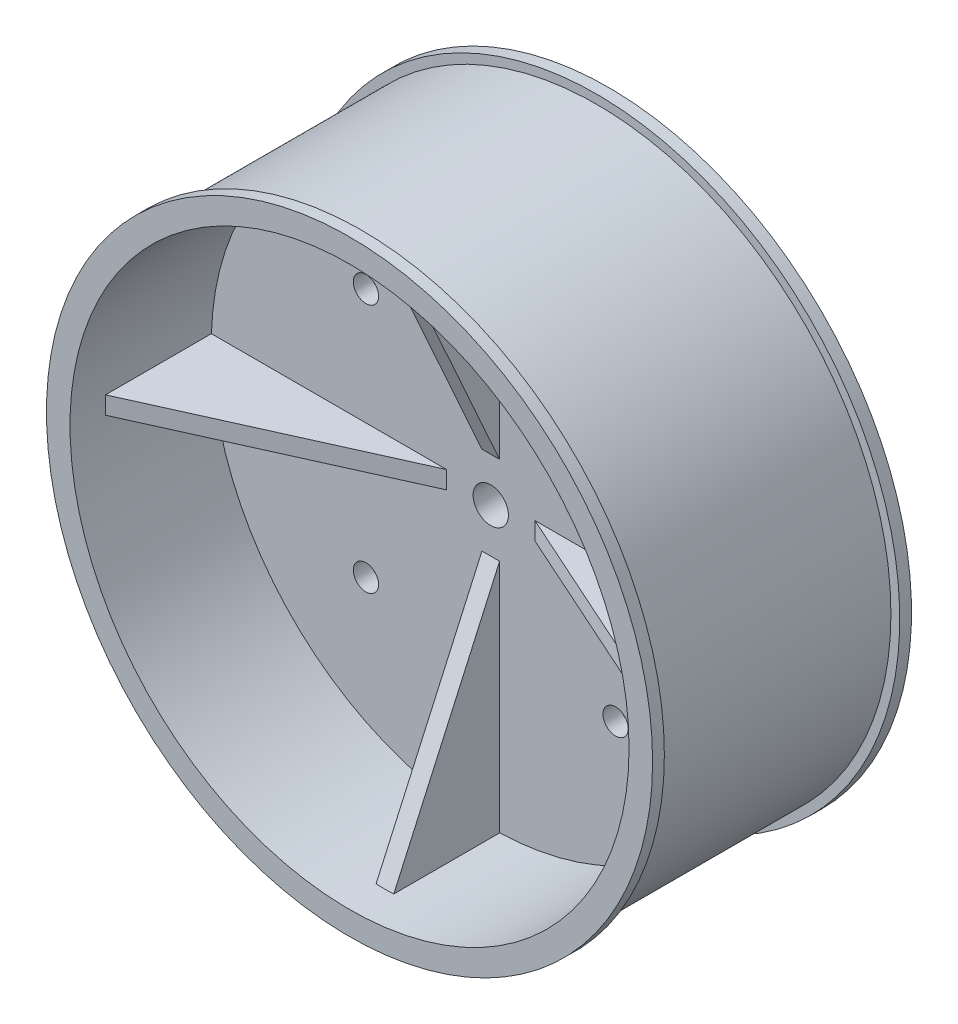
SolidWorks part; units mm, degrees
ref_plane "Front Plane" through (0, 0, 0) normal (0, 0, 1) x (1, 0, 0)
ref_plane "Top Plane" through (0, 0, 0) normal (0, 1, 0) x (1, 0, 0)
ref_plane "Right Plane" through (0, 0, 0) normal (1, 0, 0) x (0, 0, -1)
sketch "Sketch1" plane through (0, 0, 0) normal (0, 0, 1) x (1, 0, 0)
  circle A0 centre (0, 0) radius 50
  circle A1 centre (0, 0) radius 47.5
  dimension "D1" = 100
  dimension "D2" = 2.5
extrude "Boss-Extrude1" add sketch "Sketch1" along normal blind 40
sketch "Sketch2" plane through (0, 0, 40) normal (0, 0, 1) x (1, 0, 0)
  circle A0 centre (0, 0) radius 47.5
  circle A1 centre (0, 0) radius 51.5
  circle A2 centre (0, 0) radius 50 construction
  dimension "D1" = 1.5
  dimension "D2" = 95
extrude "Boss-Extrude2" add sketch "Sketch2" along normal blind 2
sketch "Sketch3" plane through (0, 0, 0) normal (0, 0, -1) x (-1, 0, 0)
  circle A0 centre (0, 0) radius 47.5
  circle A1 centre (0, 0) radius 51.5
  circle A2 centre (0, 0) radius 50 construction
  dimension "D1" = 1.5
  dimension "D2" = 95
extrude "Boss-Extrude3" add sketch "Sketch3" along normal blind 2
ref_plane "Plane1" through (0, 0, 15) normal (0, 0, -1) x (-1, 0, 0)
sketch "Sketch4" plane through (0, 0, 15) normal (0, 0, -1) x (-1, 0, 0)
  circle A0 centre (0, 0) radius 47.5
  dimension "D1" = 95
extrude "Boss-Extrude4" add sketch "Sketch4" against normal blind 3
sketch "Sketch5" plane through (0, 0, 15) normal (0, 0, -1) x (-1, 0, 0)
  circle A0 centre (0, 0) radius 8
  dimension "D1" = 16
extrude "Boss-Extrude5" add sketch "Sketch5" along normal blind 25
sketch "Sketch6" plane through (0, 0, 15) normal (0, 0, -1) x (-1, 0, 0)
  circle A0 centre (0, 0) radius 5
  dimension "D1" = 10
extrude "Boss-Extrude6" add sketch "Sketch6" along normal blind 26.25
sketch "Sketch7" plane through (0, 0, 0) normal (0, 1, 0) x (1, 0, 0)
  line L0 (0, 0) -> (0, -15) construction
  line L1 (56.65, -15) -> (-56.65, -15) construction
  line L2 (-47.5, -15) -> (-5, -15)
  line L3 (-47.5, -15) -> (-47.5, -4)
  line L4 (-47.5, -4) -> (-5, -15)
  line L5 (47.5, -15) -> (47.5, -4)
  line L6 (47.5, -4) -> (5, -15)
  line L7 (5, -15) -> (47.5, -15)
  point P8 (0, -15)
  dimension "D1" = 10
  dimension "D2" = 11
  dimension "D3" = 47.5
extrude "Boss-Extrude7" add sketch "Sketch7" along normal mid plane 3
sketch "Sketch8" plane through (0, 0, 0) normal (1, 0, 0) x (0, 0, -1)
  line L0 (0, 0) -> (-15, 0) construction
  line L1 (-15, -49) -> (-15, 49) construction
  line L2 (-15, -49) -> (-4, -49)
  line L3 (-4, -49) -> (-15, -5)
  line L4 (-15, -5) -> (-15, -49)
  line L5 (-15, 5) -> (-15, 49)
  line L6 (-15, 49) -> (-4, 49)
  line L7 (-4, 49) -> (-15, 5)
  point P6 (-15, 0)
  dimension "D1" = 15
  dimension "D2" = 98
  dimension "D3" = 11
  dimension "D4" = 10
extrude "Boss-Extrude8" add sketch "Sketch8" along normal mid plane 3
sketch "Sketch10" plane through (0, 0, 0) normal (0, 1, 0) x (1, 0, 0)
  line L0 (0, -42) -> (0, -18) construction
  line L1 (-51.5, -42) -> (51.5, -42) construction
  line L2 (-47.5, -18) -> (47.5, -18) construction
  line L3 (-47.5, -18) -> (-47.5, -36)
  line L4 (-47.5, -36) -> (-7.5, -18)
  line L5 (-7.5, -18) -> (-47.5, -18)
  line L6 (7.5, -18) -> (47.5, -18)
  line L7 (47.5, -36) -> (7.5, -18)
  line L8 (47.5, -18) -> (47.5, -36)
  point P8 (0, -18)
  dimension "D1" = 24
  dimension "D2" = 95
  dimension "D3" = 18
  dimension "D4" = 15
extrude "Boss-Extrude9" add sketch "Sketch10" along normal mid plane 3
sketch "Sketch11" plane through (0, 0, 0) normal (1, 0, 0) x (0, 0, -1)
  line L0 (-42, 0) -> (-18, 0) construction
  line L1 (-42, 47.5) -> (-42, -47.5) construction
  line L2 (-18, 47.5) -> (-18, -47.5) construction
  line L3 (-18, 47.5) -> (-36, 47.5)
  line L4 (-36, 47.5) -> (-18, 7.5)
  line L5 (-18, 7.5) -> (-18, 47.5)
  line L6 (-18, -7.5) -> (-18, -47.5)
  line L7 (-36, -47.5) -> (-18, -7.5)
  line L8 (-18, -47.5) -> (-36, -47.5)
  point P8 (-18, 0)
  dimension "D1" = 24
  dimension "D2" = 95
  dimension "D3" = 18
  dimension "D4" = 15
extrude "Boss-Extrude10" add sketch "Sketch11" along normal mid plane 3
sketch "Sketch12" plane through (0, 0, -11.25) normal (0, 0, -1) x (-1, 0, 0)
  circle A0 centre (0, 0) radius 3
  dimension "D1" = 6
extrude "Cut-Extrude1" cut sketch "Sketch12" against normal through all both and the other way through all
sketch "Sketch13" plane through (0, 0, -11.25) normal (0, 0, -1) x (-1, 0, 0)
  circle A0 centre (0, 0) radius 4
  dimension "D1" = 8
extrude "Cut-Extrude2" cut sketch "Sketch13" against normal blind 20
sketch "Sketch14" plane through (0, 0, 0) normal (0, 1, 0) x (1, 0, 0)
  line L0 (51.5, 2) -> (-51.5, 2) construction
  circle A0 centre (0, 3.5) radius 1.5
  point P4 (0, 0)
  dimension "D1" = 3
extrude "Cut-Extrude3" cut sketch "Sketch14" along normal blind 20
sketch "Sketch15" plane through (0, 0, 18) normal (0, 0, 1) x (1, 0, 0)
  line L0 (0, 0) -> (59.2017, 0) construction
  line L1 (0, 0) -> (41.5679, 41.5679) construction
  circle A0 centre (21.2132, 21.2132) radius 2.15
  circle A1 centre (21.2132, -21.2132) radius 2.15
  circle A2 centre (-21.2132, -21.2132) radius 2.15
  circle A3 centre (-21.2132, 21.2132) radius 2.15
  point P15 (0, 0)
  dimension "D2" = 4.3
  dimension "D5" = 30
  dimension "D6" = 42.4264
  dimension "D3" = 30
  dimension "D1" = 45
  dimension "D4" = 4
extrude "Cut-Extrude4" cut sketch "Sketch15" against normal through all
